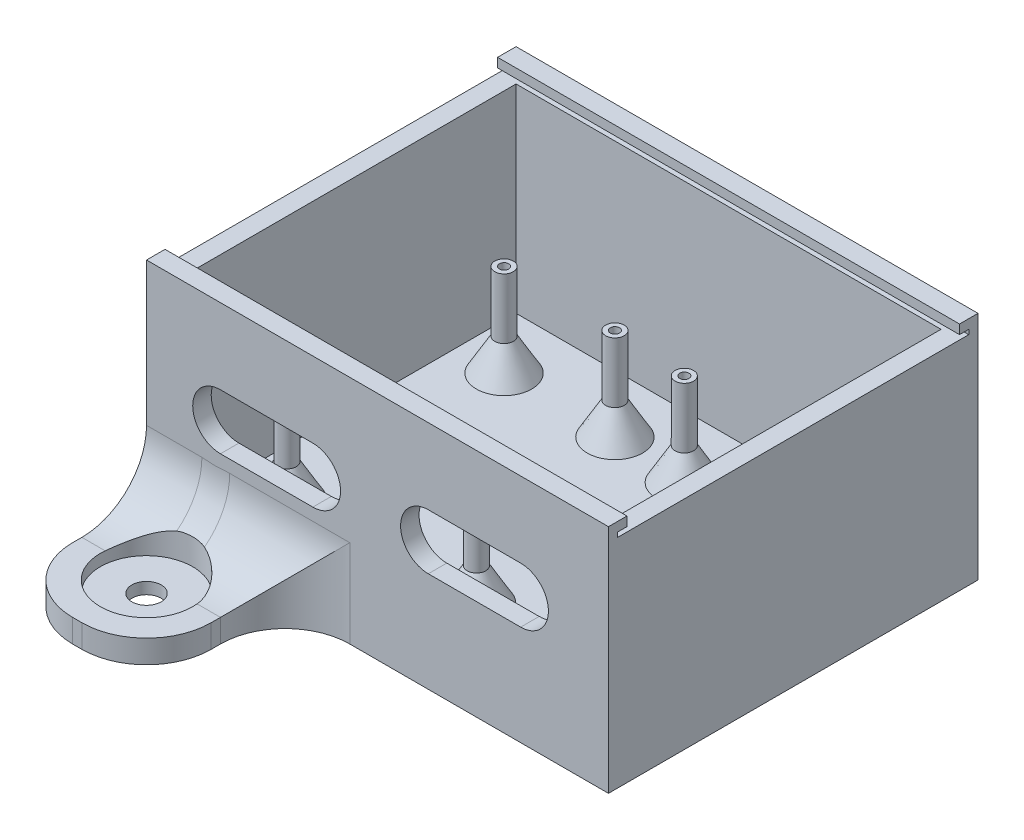
SolidWorks part; units mm, degrees
ref_plane "Front Plane" through (0, 0, 0) normal (0, 0, 1) x (1, 0, 0)
ref_plane "Top Plane" through (0, 0, 0) normal (0, 1, 0) x (1, 0, 0)
ref_plane "Right Plane" through (0, 0, 0) normal (1, 0, 0) x (0, 0, -1)
sketch "Sketch1" plane through (0, 0, 0) normal (0, 1, 0) x (1, 0, 0)
  line L1 (0, 0) -> (100, 0)
  line L2 (0, 0) -> (0, 80)
  line L3 (0, 80) -> (100, 80)
  line L4 (100, 0) -> (100, 80)
  dimension "D1" = 80
  dimension "D2" = 100
extrude "Boss-Extrude1" add sketch "Sketch1" along normal blind 50
shell "Shell1" thickness 4 removed face at (50, 50, -40)
sketch "Sketch2" plane through (0, 4, 0) normal (0, 1, 0) x (1, 0, 0)
  line L0 (96, 40) -> (4, 40) construction
  line L1 (53.9212, 62.5) -> (87.4212, 62.5) construction
  line L2 (53.9212, 62.5) -> (53.9212, 17.5) construction
  line L3 (53.9212, 17.5) -> (87.4212, 17.5) construction
  line L4 (87.4212, 62.5) -> (87.4212, 17.5) construction
  line L5 (96, 4) -> (96, 76) construction
  line L6 (4, 76) -> (4, 4) construction
  line L8 (13.899, 63.5) -> (37.899, 63.5) construction
  line L9 (13.899, 63.5) -> (13.899, 16.5) construction
  line L10 (13.899, 16.5) -> (37.899, 16.5) construction
  line L11 (37.899, 63.5) -> (37.899, 16.5) construction
  circle A0 centre (13.899, 63.5) radius 2
  circle A1 centre (37.899, 63.5) radius 2
  circle A2 centre (53.9212, 62.5) radius 2
  circle A3 centre (87.4212, 62.5) radius 2
  circle A4 centre (87.4212, 17.5) radius 2
  circle A5 centre (53.9212, 17.5) radius 2
  circle A6 centre (37.899, 16.5) radius 2
  circle A7 centre (13.899, 16.5) radius 2
  circle A8 centre (13.899, 63.5) radius 1
  circle A9 centre (37.899, 63.5) radius 1
  circle A10 centre (53.9212, 62.5) radius 1
  circle A11 centre (87.4212, 62.5) radius 1
  circle A12 centre (87.4212, 17.5) radius 1
  circle A13 centre (53.9212, 17.5) radius 1
  circle A14 centre (37.899, 16.5) radius 1
  circle A15 centre (13.899, 16.5) radius 1
  point P10 (87.4212, 40)
  point P15 (13.899, 40)
  dimension "D5" = 4
  dimension "D6" = 2
  dimension "D1" = 45
  dimension "D2" = 33.5
  dimension "D3" = 24
  dimension "D4" = 47
extrude "Boss-Extrude2" add sketch "Sketch2" along normal blind 20
chamfer "Chamfer1" distance 4 angle 60 8 edges at (87.4212, 4, -19.5) (53.9212, 4, -19.5) (37.899, 4, -18.5) (13.899, 4, -18.5) (87.4212, 4, -64.5) (53.9212, 4, -64.5) (37.899, 4, -65.5) (13.899, 4, -65.5) first distance on face at (13.899, 4, -18.5)
sketch "Sketch3" plane through (100, 0, 0) normal (1, 0, 0) x (0, 0, -1)
  line L0 (4, 50) -> (4, 48)
  line L1 (0, 50) -> (80, 50) construction
  line L2 (4, 48) -> (2, 48)
  line L3 (2, 48) -> (2, 47)
  line L4 (2, 47) -> (78, 47)
  line L5 (78, 47) -> (78, 48)
  line L6 (78, 48) -> (76, 48)
  line L7 (76, 48) -> (76, 50)
  line L8 (80, 50) -> (80, 0) construction
  line L9 (0, 50) -> (0, 0) construction
  line L10 (4, 50) -> (76, 50)
  dimension "D1" = 4
  dimension "D2" = 2
  dimension "D3" = 2
  dimension "D4" = 4
  dimension "D5" = 1
  dimension "D6" = 2
extrude "Cut-Extrude2" cut sketch "Sketch3" against normal through all
sketch "Sketch4" plane through (0, 0, 0) normal (0, 0, 1) x (1, 0, 0)
  line L1 (0, 0) -> (30, 0)
  line L2 (0, 0) -> (0, 5)
  line L3 (0, 5) -> (30, 5)
  line L4 (30, 0) -> (30, 5)
  dimension "D1" = 5
  dimension "D2" = 30
extrude "Boss-Extrude3" add sketch "Sketch4" along normal blind 30
sketch "Sketch5" plane through (0, 5, 0) normal (0, 1, 0) x (1, 0, 0)
  line L0 (15, -30) -> (15, 0) construction
  line L1 (30, -30) -> (0, -30) construction
  line L2 (30, 0) -> (0, 0) construction
  circle A0 centre (15, -15) radius 3.175
  point P9 (15, -15)
  dimension "D1" = 6.35
extrude "Cut-Extrude3" cut sketch "Sketch5" against normal through all
fillet "Fillet1" radius 14 4 edges at (15, 5, 0) (30, 2.5, 0) (0, 2.5, 30) (30, 2.5, 30)
sketch "Sketch6" plane through (0, 5, 0) normal (0, 1, 0) x (1, 0, 0)
  circle A0 centre (15, -15) radius 10
  dimension "D1" = 20
extrude "Cut-Extrude4" cut sketch "Sketch6" along normal through all and the other way blind 2.5
sketch "Sketch7" plane through (0, 0, 0) normal (0, 0, 1) x (1, 0, 0)
  line L0 (100, 27.6702) -> (0, 27.6702) construction
  line L2 (0, 50) -> (0, 19) construction
  line L3 (16, 27.6702) -> (36, 27.6702) construction
  line L4 (16, 33.6702) -> (36, 33.6702)
  line L5 (16, 21.6702) -> (36, 21.6702)
  line L6 (61, 27.6702) -> (81, 27.6702) construction
  line L7 (61, 33.6702) -> (81, 33.6702)
  line L8 (61, 21.6702) -> (81, 21.6702)
  arc A0 (16, 33.6702) -> (16, 21.6702) centre (16, 27.6702) ccw
  arc A1 (36, 21.6702) -> (36, 33.6702) centre (36, 27.6702) ccw
  arc A2 (61, 33.6702) -> (61, 21.6702) centre (61, 27.6702) ccw
  arc A3 (81, 21.6702) -> (81, 33.6702) centre (81, 27.6702) ccw
  point P2 (27.5, 27.6702)
  point P8 (26, 27.6702)
  point P13 (71, 27.6702)
  dimension "D1" = 20
  dimension "D2" = 20
  dimension "D3" = 25
  dimension "D4" = 16
  dimension "D5" = 12
extrude "Cut-Extrude5" cut sketch "Sketch7" against normal up to next
